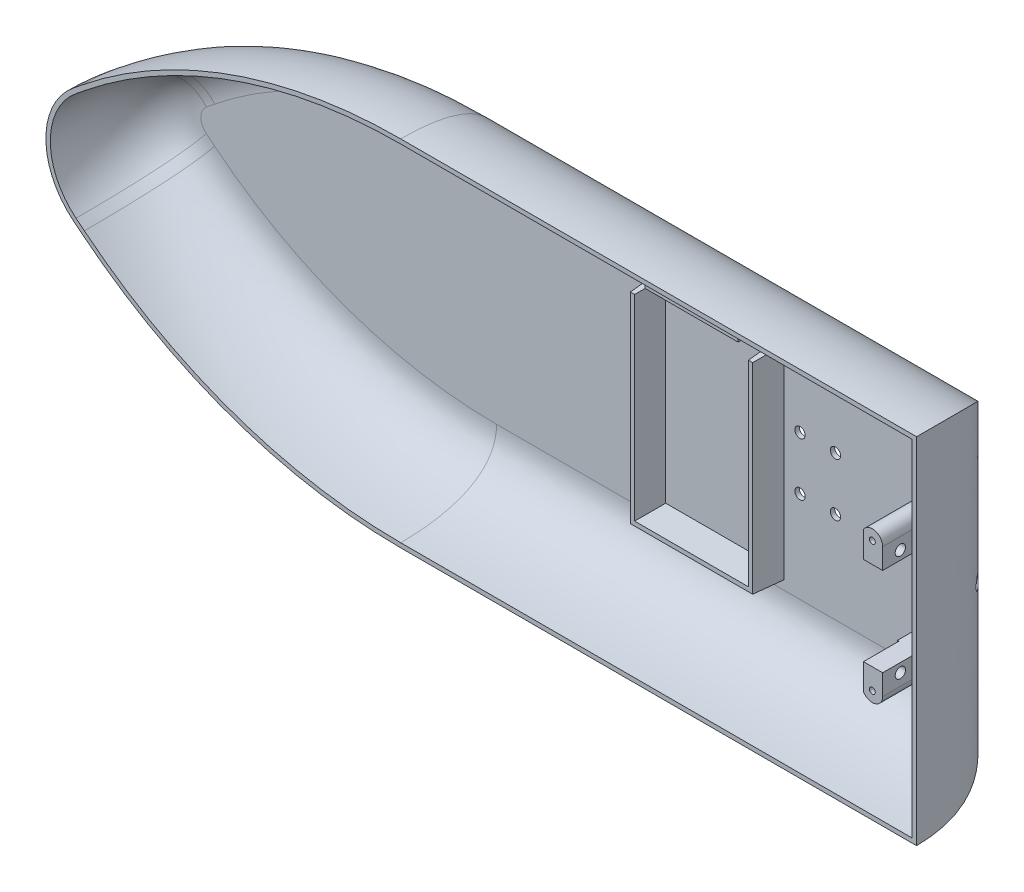
SolidWorks part; units mm, degrees
ref_plane "Plan de face" through (0, 0, 0) normal (0, 0, 1) x (1, 0, 0)
ref_plane "Plan de dessus" through (0, 0, 0) normal (0, 1, 0) x (1, 0, 0)
ref_plane "Plan de droite" through (0, 0, 0) normal (1, 0, 0) x (0, 0, -1)
sketch "Esquisse1" plane through (0, 0, 0) normal (0, 0, 1) x (1, 0, 0)
  line L0 (-4.3509, 33.8649) -> (-99.546, 33.8649) construction
  line L1 (150.454, 73.8649) -> (-4.3509, 73.8649)
  line L2 (150.454, 73.8649) -> (150.454, -6.1351)
  line L3 (150.454, -6.1351) -> (-4.3509, -6.1351)
  line L4 (-4.3509, 73.8649) -> (-4.3509, 33.8649) construction
  line L5 (-102.6925, 37.7506) -> (-99.8611, 40.0435)
  line L6 (-102.6925, 29.9791) -> (-99.8611, 27.6863)
  line L7 (-4.3509, 33.8649) -> (-4.3509, -6.1351) construction
  arc A0 (-102.6925, 37.7506) -> (-102.6925, 29.9791) centre (-99.546, 33.8649) ccw
  arc A1 (-4.3509, 73.8649) -> (-99.8611, 40.0435) centre (-4.3509, -77.9041) ccw
  arc A2 (-99.8611, 27.6863) -> (-4.3509, -6.1351) centre (-4.3509, 145.6338) ccw
  point P12 (0, 0)
  dimension "D3" = 10
  dimension "D1" = 250
  dimension "D2" = 80
extrude "Boss.-Extru.1" add sketch "Esquisse1" along normal blind 1.5
sketch "Esquisse3" plane through (0, 0, 1.5) normal (0, 0, 1) x (1, 0, 0)
  line L0 (150.454, 33.8649) -> (-104.546, 33.8649) construction
  line L1 (150.454, -6.1351) -> (150.454, 73.8649) construction
  line L2 (110.454, 66.3622) -> (110.454, 22.1054) construction
  line L3 (98.454, 66.3622) -> (98.454, 22.1054) construction
  arc A0 (-102.6925, 37.7506) -> (-102.6925, 29.9791) centre (-99.546, 33.8649) ccw construction
  circle A1 centre (98.454, 42.8649) radius 1.75
  circle A2 centre (98.454, 24.8649) radius 1.75
  circle A3 centre (110.454, 24.8649) radius 1.75
  circle A4 centre (110.454, 42.8649) radius 1.75
  dimension "D1" = 3.5
  dimension "D2" = 3.5
  dimension "D3" = 3.5
  dimension "D4" = 3.5
  dimension "D7" = 9
  dimension "D8" = 9
  dimension "D9" = 9
  dimension "D5" = 12
  dimension "D6" = 9
  dimension "D10" = 40
extrude "Enlèv. mat.-Extru.1" cut sketch "Esquisse3" against normal up to next
sketch "Esquisse4" plane through (0, 0, 1.5) normal (0, 0, -1) x (-1, 0, 0)
  line L0 (-150.454, 33.8649) -> (-3.0389, 33.8649) construction
  line L1 (-52.954, -0.6351) -> (-90.454, -0.6351)
  line L2 (-52.954, -0.6351) -> (-52.954, 65.8649)
  line L3 (-55.454, 68.3649) -> (-87.954, 68.3649)
  line L5 (-150.454, -6.1351) -> (-150.454, 73.8649) construction
  line L7 (-50.454, -3.1351) -> (-92.954, -3.1351)
  line L8 (-50.454, -3.1351) -> (-50.454, 65.8649)
  line L9 (-55.454, 70.8649) -> (-87.954, 70.8649)
  line L10 (-92.954, -3.1351) -> (-92.954, 65.8649)
  line L11 (-90.454, -0.6351) -> (-90.454, 65.8649)
  line L13 (-50.454, 65.8649) -> (-52.954, 65.8649)
  line L14 (-55.454, 70.8649) -> (-55.454, 68.3649)
  line L17 (-92.954, 65.8649) -> (-90.454, 65.8649)
  line L18 (-87.954, 70.8649) -> (-87.954, 68.3649)
  circle A0 centre (-98.454, 24.8649) radius 1.75 construction
  point P3 (-70.3996, 0.9688)
  point P4 (-51.6001, 33.8649)
  point P14 (-70.3501, 69.9688)
  dimension "D2" = 2.5
  dimension "D3" = 2.5
  dimension "D4" = 2.5
  dimension "D5" = 34.5
  dimension "D6" = 5.5
  dimension "D7" = 2.5
  dimension "D8" = 32.5
  dimension "D9" = 2.5
  dimension "D10" = 2.5
  dimension "D11" = 34.5
  dimension "D12" = 2.5
  dimension "D13" = 2.5
extrude "Boss.-Extru.2" add sketch "Esquisse4" against normal blind 10 draft 3
sketch "Esquisse7" plane through (150.454, 0, 0) normal (1, 0, 0) x (0, 0, -1)
  line L0 (0, -6.1351) -> (0, 73.8649) construction
  line L1 (-1.5, -6.1351) -> (-1.5, 73.8649) construction
  line L4 (-1.5, 73.8649) -> (0, 73.8649) construction
  line L6 (-1.5, 73.8649) -> (0, 73.8649)
  line L7 (-34, 93.8649) -> (-34, 92.3649)
  spline S0 degree 3 poles (0, 73.8649) (0, 79.7722) (-3.0996, 93.8032) (-34, 93.8649) knots 0 0 0 0 1 1 1 1
  spline S1 degree 3 poles (-34, 92.3649) (-30.8249, 92.3649) (-1.5, 92.9097) (-1.5, 73.8649) knots 0 0 0 0 1 1 1 1
  dimension "D2" = 20
  dimension "D1" = 34
sweep "Balayage1" add profiles "Esquisse7" path "Esquisse1<2>"
sketch "Esquisse1<2>" plane through (0, 0, 0) normal (0, 0, 1) x (1, 0, 0) same geometry as "Esquisse1"
sketch "Esquisse8" plane through (0, 0, 0) normal (0, 0, -1) x (-1, 0, 0)
  line L0 (-150.454, 33.8649) -> (-183.7283, 33.8649) construction
  line L2 (-155.454, 64.6793) -> (-155.454, 3.4231) construction
  line L3 (-150.454, 73.8649) -> (-150.454, -6.1351) construction
  line L4 (-150.454, -6.1351) -> (-150.454, 73.8649) construction
  circle A0 centre (-155.454, 55.8649) radius 1
  circle A1 centre (-155.454, 11.8649) radius 1
  point P2 (-150.454, 33.8649)
  dimension "D3" = 2
  dimension "D4" = 2
  dimension "D1" = 22
  dimension "D2" = 22
  dimension "D5" = 5
extrude "Enlèv. mat.-Extru.2" cut sketch "Esquisse8" against normal up to next
sketch "Esquisse9" plane through (0, 0, 34) normal (0, 0, 1) x (1, 0, 0)
  line L2 (151.954, 55.8649) -> (151.954, 48.8649)
  line L3 (151.954, 48.8649) -> (158.954, 48.8649)
  line L4 (158.954, 55.8649) -> (158.954, 48.8649)
  line L6 (158.954, 11.8649) -> (158.954, 18.8649)
  line L7 (158.954, 18.8649) -> (151.954, 18.8649)
  line L8 (151.954, 11.8649) -> (151.954, 18.8649)
  circle A0 centre (155.454, 55.8649) radius 1
  circle A1 centre (155.454, 11.8649) radius 1
  arc A2 (151.954, 11.8649) -> (158.954, 11.8649) centre (155.454, 11.8649) ccw
  arc A3 (158.954, 55.8649) -> (151.954, 55.8649) centre (155.454, 55.8649) ccw
  dimension "D1" = 2.5
  dimension "D2" = 2.5
  dimension "D3" = 2
  dimension "D4" = 2
  dimension "D5" = 30
extrude "Boss.-Extru.3" add sketch "Esquisse9" against normal up to next
sketch "Esquisse10" plane through (0, 0, 34) normal (0, 0, 1) x (1, 0, 0)
  line L0 (152.454, 10.0621) -> (152.454, 18.8649)
  line L2 (152.454, 48.8649) -> (152.454, 57.6676)
  line L3 (151.954, 48.8649) -> (158.954, 48.8649) construction
  line L4 (151.954, 55.8649) -> (151.954, 48.8649) construction
  line L5 (151.954, 55.8649) -> (151.954, 48.8649)
  line L6 (152.454, 48.8649) -> (151.954, 48.8649)
  line L7 (158.954, 18.8649) -> (151.954, 18.8649) construction
  line L8 (151.954, 18.8649) -> (151.954, 11.8649) construction
  line L9 (152.454, 18.8649) -> (151.954, 18.8649)
  line L10 (151.954, 18.8649) -> (151.954, 11.8649)
  line L11 (150.454, 73.8649) -> (150.454, -6.1351) construction
  circle A0 centre (155.454, 55.8649) radius 3.5 construction
  circle A1 centre (155.454, 11.8649) radius 3.5 construction
  arc A2 (158.954, 55.8649) -> (151.954, 55.8649) centre (155.454, 55.8649) ccw construction
  arc A3 (151.954, 11.8649) -> (158.954, 11.8649) centre (155.454, 11.8649) ccw construction
  arc A4 (152.454, 57.6676) -> (151.954, 55.8649) centre (155.454, 55.8649) ccw
  arc A5 (151.954, 11.8649) -> (152.454, 10.0621) centre (155.454, 11.8649) ccw
  dimension "D1" = 2
extrude "Enlèv. mat.-Extru.3" cut sketch "Esquisse10" against normal blind 12
sketch "Esquisse11" plane through (152.454, 0, 0) normal (-1, 0, 0) x (0, 0, 1)
  line L0 (28, 48.8649) -> (28, 18.8649) construction
  line L4 (22, 48.8649) -> (34, 48.8649) construction
  line L5 (22, 18.8649) -> (34, 18.8649) construction
  line L6 (28, 48.8649) -> (28, 51.8649) construction
  line L7 (28, 15.8649) -> (28, 18.8649) construction
  circle A0 centre (28, 51.8649) radius 1.75
  circle A1 centre (28, 15.8649) radius 1.75
  point P6 (28, 48.8649)
  point P7 (28, 18.8649)
  dimension "D1" = 3.5
  dimension "D2" = 3.5
  dimension "D3" = 36
extrude "Enlèv. mat.-Extru.4" cut sketch "Esquisse11" against normal up to next
sketch "Esquisse16" plane through (151.954, 0, 0) normal (-1, 0, 0) x (0, 0, 1)
  line L0 (1.563, 48.8649) -> (1.563, 55.8649) construction
  line L1 (1.563, 38.8649) -> (16.563, 38.8649)
  line L2 (1.563, 38.8649) -> (1.563, 28.8649)
  line L3 (1.563, 28.8649) -> (16.563, 28.8649)
  line L4 (16.563, 38.8649) -> (16.563, 28.8649)
  line L6 (1.563, 48.8649) -> (22, 48.8649) construction
  line L7 (1.563, 18.8649) -> (22, 18.8649) construction
  line L8 (16.563, 38.8649) -> (16.563, 48.8649) construction
  line L9 (16.563, 28.8649) -> (16.563, 18.8649) construction
  dimension "D1" = 15
  dimension "D2" = 10
extrude "Boss.-Extru.4" add sketch "Esquisse16" against normal up to surface (14.8929 mm away) up to face at (155.7232, 14.4904, 2.641)
sketch "Esquisse12" plane through (202.3426, 0, -73.6467) normal (0.9397, 0, -0.342) x (-0.342, 0, -0.9397)
  circle A0 centre (-61.7525, 33.8649) radius 2.25
  dimension "D1" = 4.5
extrude "Enlèv. mat.-Extru.5" cut sketch "Esquisse12" against normal up to surface (75.2795 mm away) up to face at (151.954, 33.8649, 9.063)
sketch "Esquisse17" plane through (0, 0, 16.563) normal (0, 0, 1) x (1, 0, 0)
  line L0 (166.8469, 38.8649) -> (151.954, 38.8649) construction
  line L1 (156.954, 38.8649) -> (160.954, 38.8649)
  line L2 (156.954, 38.8649) -> (156.954, 28.8649)
  line L3 (156.954, 28.8649) -> (160.954, 28.8649)
  line L4 (160.954, 38.8649) -> (160.954, 28.8649)
  line L5 (166.8469, 28.8649) -> (151.954, 28.8649) construction
  line L6 (151.954, 28.8649) -> (151.954, 38.8649) construction
  point P8 (151.954, 33.8649)
  dimension "D1" = 4
  dimension "D2" = 5
extrude "Enlèv. mat.-Extru.6" cut sketch "Esquisse17" against normal blind 8
